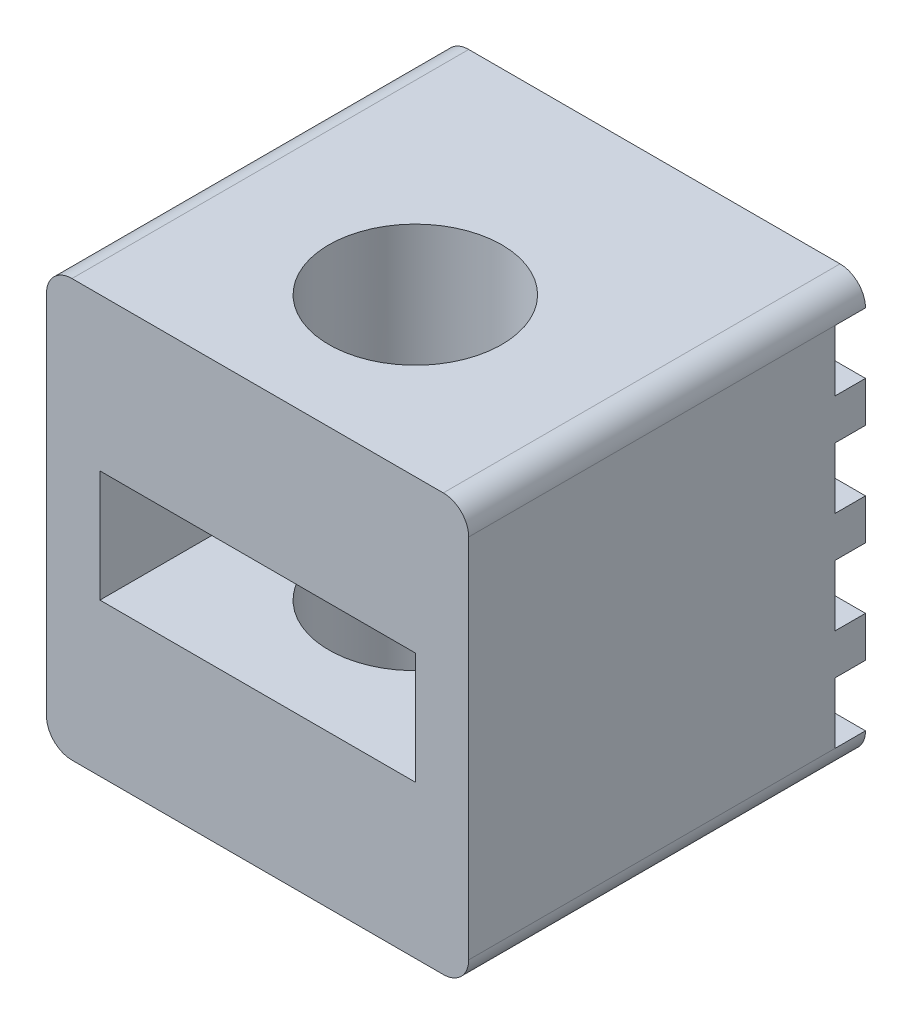
SolidWorks part; units mm, degrees
ref_plane "Front Plane" through (0, 0, 0) normal (0, 0, 1) x (1, 0, 0)
ref_plane "Top Plane" through (0, 0, 0) normal (0, 1, 0) x (1, 0, 0)
ref_plane "Right Plane" through (0, 0, 0) normal (1, 0, 0) x (0, 0, -1)
sketch "Sketch1" plane through (0, 0, 0) normal (0, 1, 0) x (1, 0, 0)
  line L1 (-4.15, -3.9) -> (4.15, -3.9)
  line L2 (-4.15, -3.9) -> (-4.15, 3.9)
  line L3 (-4.15, 3.9) -> (4.15, 3.9)
  line L4 (4.15, -3.9) -> (4.15, 3.9)
  line L5 (-4.15, -3.9) -> (4.15, 3.9) construction
  line L6 (-4.15, 3.9) -> (4.15, -3.9) construction
  point P0 (0, 0)
  dimension "D1" = 7.8
  dimension "D2" = 8.3
extrude "Boss-Extrude1" add sketch "Sketch1" along normal mid plane 8.2
sketch "Sketch2" plane through (-4.15, 0, 0) normal (-1, 0, 0) x (0, 0, 1)
  line L0 (-8.9, 3.6) -> (-3.3, 3.6)
  line L1 (-3.3, 3.6) -> (-3.3, 2.4)
  line L2 (-3.3, 2.4) -> (-3.9, 2.4)
  line L3 (-3.9, 2.4) -> (-3.9, 1.6)
  line L4 (-3.9, 1.6) -> (-3.3, 1.6)
  line L5 (-3.3, 1.6) -> (-3.3, 0.4)
  line L6 (-3.3, 0.4) -> (-3.9, 0.4)
  line L7 (-3.9, 0.4) -> (-3.9, -0.4)
  line L8 (-3.9, -0.4) -> (-3.3, -0.4)
  line L9 (-3.3, -0.4) -> (-3.3, -1.6)
  line L10 (-3.3, -1.6) -> (-3.9, -1.6)
  line L11 (-3.9, -1.6) -> (-3.9, -2.4)
  line L12 (-3.9, -2.4) -> (-3.3, -2.4)
  line L13 (-3.3, -2.4) -> (-3.3, -3.6)
  line L14 (-3.3, -3.6) -> (-8.9, -3.6)
  line L15 (-3.9, 4.1) -> (-3.9, -4.1) construction
  line L16 (-8.9, 3.6) -> (-8.9, -3.6)
  point P19 (-3.9, 0)
  dimension "D1" = 1.2
  dimension "D2" = 0.8
  dimension "D3" = 0.6
  dimension "D4" = 5
extrude "Cut-Extrude1" cut sketch "Sketch2" against normal through all
sketch "Sketch4" plane through (0, 0, 3.9) normal (0, 0, 1) x (1, 0, 0)
  line L1 (-3.1, -1.1) -> (3.1, -1.1)
  line L2 (-3.1, -1.1) -> (-3.1, 1.1)
  line L3 (-3.1, 1.1) -> (3.1, 1.1)
  line L4 (3.1, -1.1) -> (3.1, 1.1)
  line L5 (-3.1, -1.1) -> (3.1, 1.1) construction
  line L6 (-3.1, 1.1) -> (3.1, -1.1) construction
  point P0 (0, 0)
  dimension "D1" = 2.2
  dimension "D2" = 6.2
extrude "Cut-Extrude2" cut sketch "Sketch4" against normal blind 6.2
sketch "Sketch5" plane through (0, -4.1, 0) normal (0, -1, 0) x (1, 0, 0)
  line L0 (0, -14.9504) -> (0, 14.9504) construction
  line L1 (-4.15, 3.9) -> (4.15, 3.9) construction
  circle A0 centre (0, 0.8) radius 1.7
  dimension "D1" = 3.4
  dimension "D2" = 3.1
extrude "Cut-Extrude3" cut sketch "Sketch5" against normal through all
fillet "Fillet1" radius 0.5 4 edges at (4.15, 4.1, 0) (4.15, -4.1, 0) (-4.15, 4.1, 0) (-4.15, -4.1, 0)
equation "\"M3_d\"= 3.4"
equation "\"M3_nut_s_XY\"= 6.2"
equation "\"M3_nut_m_XY\"= 2.2"
equation "\"tensioner_h\"= 7.8"
equation "\"tensioner_b\"= 8.3"
equation "\"t\"= 3"
equation "\"D1@Sketch1\"=\"tensioner_h\""
equation "\"D2@Sketch1\"=\"tensioner_b\""
equation "\"D1@Boss-Extrude1\"=\"t\" + \"M3_nut_m_XY\" + \"t\""
equation "\"D1@Sketch4\"=\"M3_nut_m_XY\""
equation "\"D2@Sketch4\"=\"M3_nut_s_XY\""
equation "\"D1@Cut-Extrude2\"=\"M3_nut_s_XY\""
equation "\"D1@Sketch5\"=\"M3_d\""
equation "\"D2@Sketch5\"=\"M3_nut_s_XY\" / 2"
